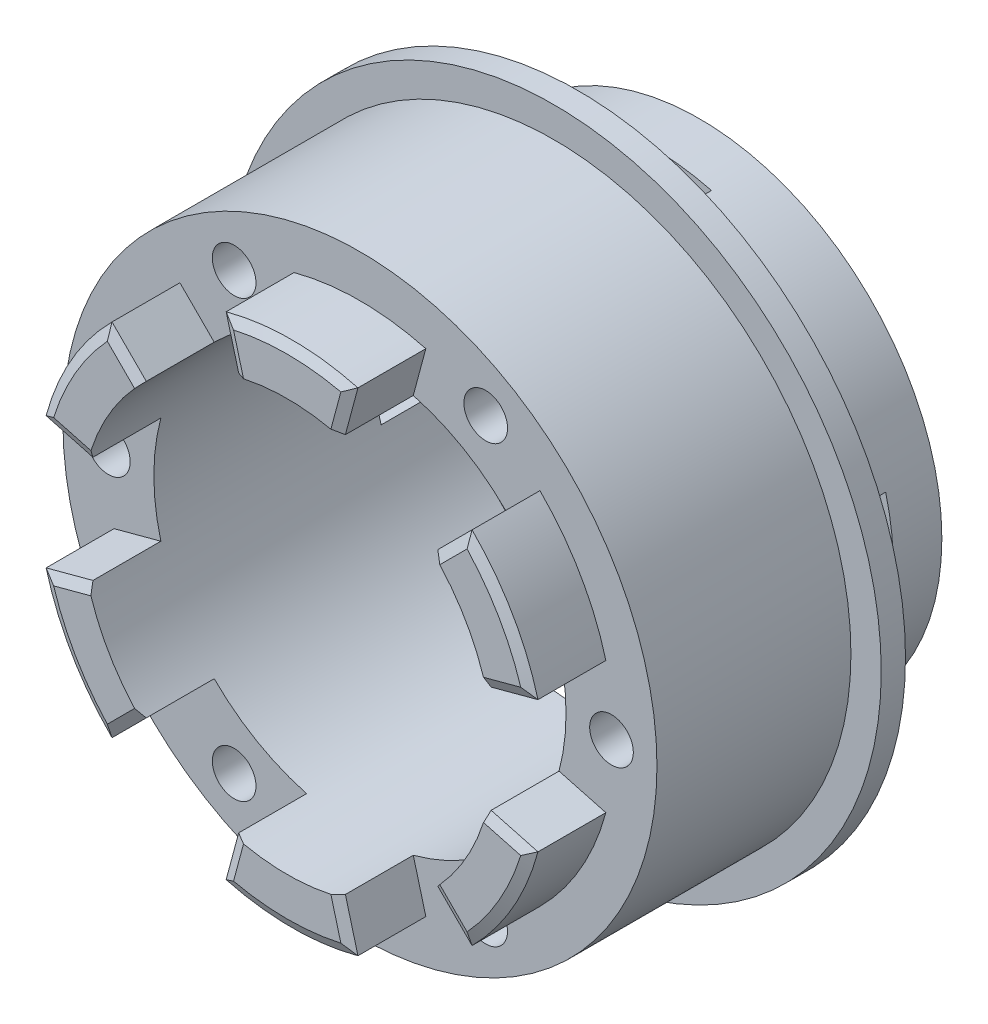
SolidWorks part; units mm, degrees
ref_plane "정면" through (0, 0, 0) normal (0, 0, 1) x (1, 0, 0)
ref_plane "윗면" through (0, 0, 0) normal (0, 1, 0) x (1, 0, 0)
ref_plane "우측면" through (0, 0, 0) normal (1, 0, 0) x (0, 0, -1)
sketch "스케치1" plane through (0, 0, 0) normal (0, 0, 1) x (1, 0, 0)
  circle A0 centre (0, 0) radius 10
  dimension "D1" = 20
extrude "보스-돌출1" add sketch "스케치1" along normal blind 2
sketch "스케치2" plane through (0, 0, 2) normal (0, 0, 1) x (1, 0, 0)
  circle A0 centre (0, 0) radius 10
  circle A1 centre (0, 0) radius 8.5
  circle A5 centre (0, 0) radius 10 construction
  dimension "D1" = 1.5
extrude "보스-돌출2" add sketch "스케치2" along normal blind 3
sketch "스케치4" plane through (0, 0, 5) normal (0, 0, 1) x (1, 0, 0)
  circle A0 centre (0, 0) radius 13.5
  circle A1 centre (0, 0) radius 8.5
  circle A2 centre (0, 0) radius 8.5 construction
  dimension "D1" = 27
extrude "보스-돌출3" add sketch "스케치4" along normal blind 1
sketch "스케치5" plane through (0, 0, 6) normal (0, 0, 1) x (1, 0, 0)
  circle A0 centre (0, 0) radius 8.5
  circle A1 centre (0, 0) radius 12.25
  circle A2 centre (0, 0) radius 8.5 construction
  dimension "D1" = 24.5
extrude "보스-돌출4" add sketch "스케치5" along normal blind 8
sketch "스케치6" plane through (0, 0, 14) normal (0, 0, 1) x (1, 0, 0)
  circle A0 centre (0, 0) radius 10.375 construction
  circle A6 centre (0, 0) radius 8.5 construction
  circle A8 centre (10.375, 0) radius 0.9
  circle A9 centre (5.1875, -8.985) radius 0.9
  circle A10 centre (-5.1875, -8.985) radius 0.9
  circle A11 centre (-10.375, 0) radius 0.9
  circle A12 centre (-5.1875, 8.985) radius 0.9
  circle A13 centre (5.1875, 8.985) radius 0.9
  point P19 (0, 0)
  point P20 (0, 0)
  dimension "D1" = 1.875
  dimension "D2" = 1.8
  dimension "D3" = 6
extrude "컷-돌출1" cut sketch "스케치6" against normal blind 8
sketch "스케치7" plane through (0, 0, 0) normal (0, 0, -1) x (-1, 0, 0)
  circle A0 centre (0, 0) radius 7 construction
  circle A5 centre (0, 0) radius 3
  circle A6 centre (-7, 0) radius 1.15
  circle A7 centre (7, 0) radius 1.15
  circle A9 centre (0, 7) radius 1.15
  circle A11 centre (0, -7) radius 1.15
  dimension "D1" = 14
  dimension "D2" = 2.3
  dimension "D4" = 6
extrude "컷-돌출2" cut sketch "스케치7" against normal through all
sketch "스케치8" plane through (0, 0, 0) normal (0, 1, 0) x (1, 0, 0)
  line L0 (10, 0) -> (-10, 0) construction
  line L1 (-2.5, -2) -> (2.5, -2)
  line L2 (-2.5, -2) -> (-2.5, -5)
  line L3 (-2.5, -5) -> (2.5, -5)
  line L4 (2.5, -2) -> (2.5, -5)
  line L5 (-2.5, -2) -> (2.5, -5) construction
  line L6 (-2.5, -5) -> (2.5, -2) construction
  line L8 (10, -5) -> (10, 0) construction
  line L9 (-10, 0) -> (-10, -5) construction
  line L10 (10, -5) -> (-10, -5) construction
  point P0 (0, -3.5)
  dimension "D1" = 2
  dimension "D3" = 7.5
  dimension "D4" = 7.5
extrude "컷-돌출3" cut sketch "스케치8" against normal through all both and the other way through all
sketch "스케치9" plane through (0, 0, 0) normal (1, 0, 0) x (0, 0, -1)
  line L0 (-5, -9.6825) -> (-5, 9.6825) construction
  line L1 (-5, -2.5) -> (-2, -2.5)
  line L2 (-5, -2.5) -> (-5, 2.5)
  line L3 (-5, 2.5) -> (-2, 2.5)
  line L4 (-2, -2.5) -> (-2, 2.5)
  line L5 (0, 10) -> (-2, 10) construction
  line L6 (-2, -10) -> (0, -10) construction
  line L7 (0, -10) -> (0, 10) construction
  dimension "D1" = 7.5
  dimension "D2" = 7.5
  dimension "D3" = 2
extrude "컷-돌출4" cut sketch "스케치9" against normal through all both and the other way through all
sketch "스케치10" plane through (0, 0, 14) normal (0, 0, 1) x (1, 0, 0)
  line L1 (2.2, 8.2104) -> (2.7176, 10.1422)
  line L3 (6.0104, 6.0104) -> (7.4246, 7.4246)
  line L5 (8.2104, 2.2) -> (10.1422, 2.7176)
  line L7 (8.2104, -2.2) -> (10.1422, -2.7176)
  line L9 (6.0104, -6.0104) -> (7.4246, -7.4246)
  line L11 (2.2, -8.2104) -> (2.7176, -10.1422)
  line L13 (-2.2, -8.2104) -> (-2.7176, -10.1422)
  line L15 (-6.0104, -6.0104) -> (-7.4246, -7.4246)
  line L17 (-8.2104, -2.2) -> (-10.1422, -2.7176)
  line L19 (-8.2104, 2.2) -> (-10.1422, 2.7176)
  line L21 (-6.0104, 6.0104) -> (-7.4246, 7.4246)
  line L23 (-2.2, 8.2104) -> (-2.7176, 10.1422)
  arc A0 (-7.4246, 7.4246) -> (-10.1422, 2.7176) centre (0, 0) ccw
  arc A1 (-8.2104, -2.2) -> (-6.0104, -6.0104) centre (0, 0) ccw
  arc A2 (2.7176, 10.1422) -> (-2.7176, 10.1422) centre (0, 0) ccw
  arc A3 (10.1422, 2.7176) -> (7.4246, 7.4246) centre (0, 0) ccw
  arc A4 (7.4246, -7.4246) -> (10.1422, -2.7176) centre (0, 0) ccw
  arc A5 (-2.7176, -10.1422) -> (2.7176, -10.1422) centre (0, 0) ccw
  arc A6 (-10.1422, -2.7176) -> (-7.4246, -7.4246) centre (0, 0) ccw
  arc A7 (-2.2, -8.2104) -> (2.2, -8.2104) centre (0, 0) ccw
  arc A8 (6.0104, -6.0104) -> (8.2104, -2.2) centre (0, 0) ccw
  arc A9 (8.2104, 2.2) -> (6.0104, 6.0104) centre (0, 0) ccw
  arc A10 (2.2, 8.2104) -> (-2.2, 8.2104) centre (0, 0) ccw
  arc A11 (-6.0104, 6.0104) -> (-8.2104, 2.2) centre (0, 0) ccw
  circle A12 centre (0, 0) radius 8.5 construction
  arc A13 (8.124, 2.5) -> (2.5, 8.124) centre (0, 0) ccw construction
  point P30 (0, 0)
  dimension "D1" = 2
extrude "보스-돌출5" add sketch "스케치10" along normal blind 3
chamfer "모따기1" distance 0.2 angle 64 18 edges at (-9.1763, -2.4588, 17) (-6.7175, -6.7175, 17) (-2.4588, -9.1763, 17) (2.4588, -9.1763, 17) (6.7175, -6.7175, 17) (9.1763, -2.4588, 17) (9.1763, 2.4588, 17) (6.7175, 6.7175, 17) (2.4588, 9.1763, 17) (-2.4588, 9.1763, 17) (-6.7175, 6.7175, 17) (-9.1763, 2.4588, 17) (-9.0933, -5.25, 17) (0, -10.5, 17) (9.0933, -5.25, 17) (9.0933, 5.25, 17) (0, 10.5, 17) (-9.0933, 5.25, 17) first distance on face at (-9.1763, -2.4588, 15.5) first distance on face at (-6.7175, -6.7175, 15.5) first distance on face at (-2.4588, -9.1763, 15.5) first distance on face at (2.4588, -9.1763, 15.5) first distance on face at (6.7175, -6.7175, 15.5) first distance on face at (9.1763, -2.4588, 15.5) first distance on face at (9.1763, 2.4588, 15.5) first distance on face at (6.7175, 6.7175, 15.5) first distance on face at (2.4588, 9.1763, 15.5) first distance on face at (-2.4588, 9.1763, 15.5) first distance on face at (-6.7175, 6.7175, 15.5) first distance on face at (-9.1763, 2.4588, 15.5) first distance on face at (-8.9383, -5.1606, 15.5) first distance on face at (0, -10.3211, 15.5) first distance on face at (8.9383, -5.1606, 15.5) first distance on face at (8.9383, 5.1606, 15.5) first distance on face at (0, 10.3211, 15.5) first distance on face at (-8.9383, 5.1606, 15.5)
